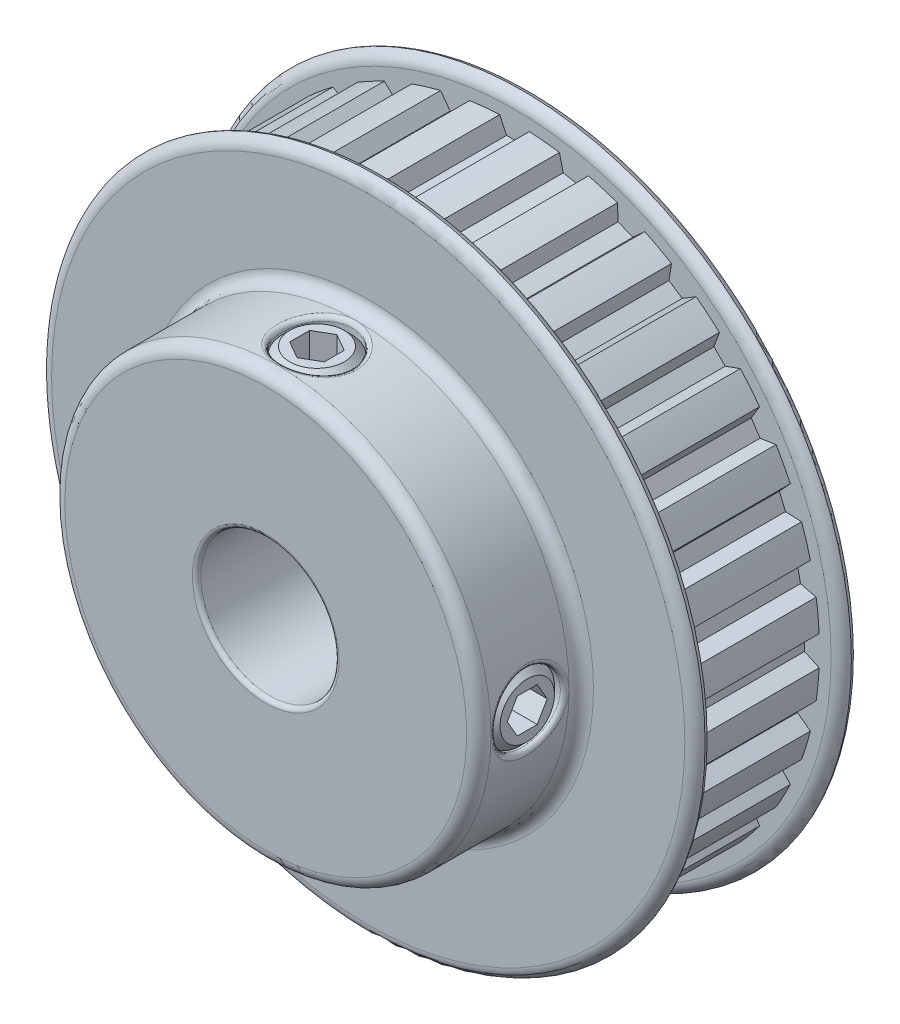
SolidWorks part; units mm, degrees
ref_plane "Front Plane" through (0, 0, 0) normal (0, 0, 1) x (1, 0, 0)
ref_plane "Top Plane" through (0, 0, 0) normal (0, 1, 0) x (1, 0, 0)
ref_plane "Right Plane" through (0, 0, 0) normal (1, 0, 0) x (0, 0, -1)
sketch "Sketch1" plane through (0, 0, 0) normal (0, 0, 1) x (1, 0, 0)
  line L0 (-1.2827, 26.4496) -> (-0.6905, 25.1796)
  line L1 (-0.6905, 25.1796) -> (0.6905, 25.1796)
  line L2 (0.6905, 25.1796) -> (1.2827, 26.4496)
  line L3 (-1.2827, 26.4496) -> (1.2827, 26.4496)
  line L4 (0, 0) -> (0, 25.1796) construction
  line L5 (0, 25.1796) -> (0, 27.4656) construction
  circle A0 centre (0, 0) radius 25.85 construction
  circle A1 centre (0, 0) radius 28.5 construction
  circle A2 centre (0, 0) radius 26.4807 construction
  point P6 (0, 26.4496)
  point P11 (0, 25.85)
  point P13 (0, 28.5)
  point P14 (0, 26.4807)
  dimension "Pitch Diameter" = 51.7
  dimension "OD" = 57
  dimension "D5" = 50
  dimension "D6" = 2.5654
  dimension "D4" = 1.27
  dimension "D3" = 2.286
  dimension "D2" = 1.6156
sketch "Sketch2" plane through (0, 0, 0) normal (1, 0, 0) x (0, 0, -1)
  line L0 (-11.55, 6) -> (11.55, 6) construction
  line L1 (-11.55, 6) -> (-11.55, 18.5) construction
  line L2 (-11.55, 18.5) -> (-2.65, 18.5) construction
  line L3 (-2.65, 18.5) -> (-2.65, 28.5) construction
  line L4 (-2.65, 28.5) -> (-1.15, 28.5) construction
  line L5 (-1.15, 28.5) -> (-1.15, 26.4807) construction
  line L6 (-1.15, 26.4807) -> (10.05, 26.4807) construction
  line L7 (10.05, 26.4807) -> (10.05, 28.5) construction
  line L8 (10.05, 28.5) -> (11.55, 28.5) construction
  line L9 (11.55, 28.5) -> (11.55, 6) construction
  line L10 (-11.55, 0) -> (11.55, 0) construction
  line L13 (-2.65, 28.5) -> (-1.9, 28.5) construction
  line L14 (-1.15, 27.4904) -> (-1.15, 26.4807) construction
  line L15 (10.05, 26.4807) -> (10.05, 27.4904) construction
  line L16 (10.8, 28.5) -> (11.55, 28.5) construction
  arc A0 (-1.15, 27.4904) -> (-1.9, 28.5) centre (-2.2046, 27.4904) ccw construction
  arc A1 (10.05, 27.4904) -> (10.8, 28.5) centre (11.1046, 27.4904) cw construction
  point P12 (-1.15, 27.4904)
  point P14 (-1.9, 28.5)
  point P20 (10.05, 27.4904)
  point P21 (10.8, 28.5)
  point P25 (10.05, 0)
  point P26 (-1.15, 0)
  dimension "Overall Width" = 23.1
  dimension "Outside Width" = 14.2
  dimension "Inside Width" = 11.2
  dimension "Hub Diameter" = 37
  dimension "For Shaft Diameter" = 12
sketch "Sketch7" plane through (0, 0, 0) normal (1, 0, 0) x (0, 0, -1)
  line L0 (-11.55, 6) -> (-11.55, 18.5) construction
  line L1 (-11.55, 18.5) -> (-2.65, 18.5) construction
  line L2 (-2.65, 18.5) -> (-2.65, 28.5) construction
  line L3 (-2.65, 28.5) -> (-1.9, 28.5) construction
  line L4 (-1.15, 27.4904) -> (-1.15, 26.4807) construction
  line L5 (-1.15, 26.4807) -> (10.05, 26.4807) construction
  line L6 (10.05, 26.4807) -> (10.05, 27.4904) construction
  line L7 (10.8, 28.5) -> (11.55, 28.5) construction
  line L8 (11.55, 28.5) -> (11.55, 6) construction
  line L9 (-11.55, 6) -> (11.55, 6) construction
  line L10 (-11.55, 6) -> (-11.55, 18.5)
  line L11 (-11.55, 18.5) -> (-2.65, 18.5)
  line L12 (-2.65, 18.5) -> (-2.65, 28.5)
  line L13 (-2.65, 28.5) -> (-1.9, 28.5)
  line L14 (-1.15, 27.4904) -> (-1.15, 26.4807)
  line L15 (-1.15, 26.4807) -> (10.05, 26.4807)
  line L16 (10.05, 26.4807) -> (10.05, 27.4904)
  line L17 (10.8, 28.5) -> (11.55, 28.5)
  line L18 (11.55, 28.5) -> (11.55, 6)
  line L19 (-11.55, 6) -> (11.55, 6)
  arc A0 (-1.15, 27.4904) -> (-1.9, 28.5) centre (-2.2046, 27.4904) ccw construction
  arc A1 (10.8, 28.5) -> (10.05, 27.4904) centre (11.1046, 27.4904) ccw construction
  arc A2 (-1.15, 27.4904) -> (-1.9, 28.5) centre (-2.2046, 27.4904) ccw
  arc A3 (10.8, 28.5) -> (10.05, 27.4904) centre (11.1046, 27.4904) ccw
revolve "Revolve1" add sketch "Sketch7" angle 360 about L10
sketch "Sketch3" plane through (0, 0, 0) normal (0, 0, 1) x (1, 0, 0)
  line L0 (-0.6905, 25.1796) -> (0.6905, 25.1796) construction
  line L1 (0.6905, 25.1796) -> (1.2827, 26.4496) construction
  line L2 (-1.2827, 26.4496) -> (-0.6905, 25.1796) construction
  line L3 (-0.6905, 25.1796) -> (0.6905, 25.1796)
  line L4 (0.6905, 25.1796) -> (1.2827, 26.4496)
  line L5 (-1.2827, 26.4496) -> (-0.6905, 25.1796)
  arc A1 (1.2827, 26.4496) -> (-1.2827, 26.4496) centre (0, 0) ccw
  circle A2 centre (0, 0) radius 26.4807 construction
extrude "Cut-Extrude1" cut sketch "Sketch3" against normal up to vertex (10.05 mm away) from vertex up to point (0, 26.4807, -10.05) starting at point (0, 26.4807, 1.15)
pattern_circular "CirPattern1" count 32 over 360 about axis through (0, 0, 11.55) along (0, 0, -1) of "Cut-Extrude1" reverse direction yes
sketch "Sketch4" plane through (0, 0, 0) normal (0, 1, 0) x (1, 0, 0)
  line L0 (0, -2.65) -> (0, -11.55) construction
  line L3 (0, -11.55) -> (0, 11.55) construction
  line L4 (-18.5, -2.65) -> (18.5, -2.65) construction
  line L5 (-18.5, -11.55) -> (18.5, -11.55) construction
  circle A0 centre (0, -7.1) radius 3
  dimension "D1" = 6
extrude "Cut-Extrude2" cut sketch "Sketch4" along normal through all
ref_plane "Plane1" through (0, 0, 7.1) normal (0, 0, 1) x (1, 0, 0)
sketch "Sketch5" plane through (0, 0, 7.1) normal (0, 0, 1) x (1, 0, 0)
  line L0 (0, 0) -> (0, 18.5) construction
  line L1 (-3, 18.2551) -> (-3, 5.1962) construction
  line L2 (-3, 18.2551) -> (-3, 5.1962) construction
  line L3 (0, 18.2551) -> (0, 6)
  line L4 (0, 6) -> (-2.365, 6)
  line L5 (-3, 17.6201) -> (-3, 6.635)
  line L6 (-2.365, 18.2551) -> (0, 18.2551)
  line L7 (-3, 17.6201) -> (-2.365, 18.2551)
  line L8 (-3, 6.635) -> (-2.365, 6)
  line L9 (0, 28.5) -> (0, 6) construction
  line L10 (0, 6) -> (0, 18.5) construction
  point P13 (-3, 6)
  point P15 (-3, 18.2551)
revolve "Revolve2" add sketch "Sketch5" angle 360 mid plane about L0
sketch "Sketch6" plane through (0, 18.2551, 0) normal (0, -1, 0) x (-1, 0, 0)
  line L1 (0, -5.3679) -> (-1.5, -6.234)
  line L2 (-1.5, -6.234) -> (-1.5, -7.966)
  line L3 (-1.5, -7.966) -> (0, -8.8321)
  line L4 (0, -8.8321) -> (1.5, -7.966)
  line L5 (1.5, -7.966) -> (1.5, -6.234)
  line L6 (1.5, -6.234) -> (0, -5.3679)
  circle A0 centre (0, -7.1) radius 1.5 construction
  dimension "D1" = 3
extrude "Cut-Extrude3" cut sketch "Sketch6" along normal blind 2.25
pattern_circular "CirPattern2" count 2 every 90 about axis through (0, 0, 11.55) along (0, 0, -1) of "Cut-Extrude2", "Revolve2", "Cut-Extrude3"
fillet "Fillet1" radius 1.0571 4 edges at (28.5, 0, -11.55) (28.5, 0, 2.65) (18.5, 0, 2.65) (18.5, 0, 11.55)
fillet "Fillet2" radius 0.37 4 edges at (6, 0, 11.55) (18.4887, -0.6459, 10.0296) (0.6459, 18.4887, 10.0296) (6, 0, -11.55)
equation "\"D1@Sketch4\" = \"For Shaft Diameter@Sketch2\"/2"
equation "\"D1@Sketch6\" = \"D1@Sketch4\"/2"
equation "\"D1@Cut-Extrude3\" = \"D1@Sketch6\"*.75"
equation "\"D1@Fillet1\"=\"Hub Diameter@Sketch2\" / 35"
equation "\"D2@Sketch1\"=\"Pitch Diameter@Sketch1\"/32"
equation "\"D1@Fillet2\"=\"Hub Diameter@Sketch2\"*.01"
